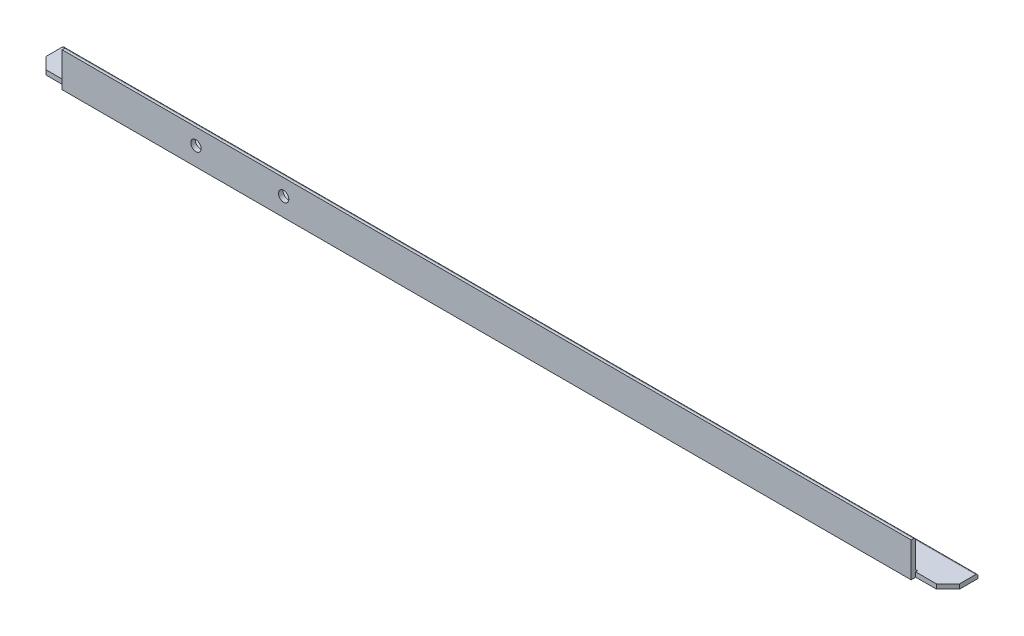
SolidWorks part; units mm, degrees
material "1060 Сплав"
ref_plane "Front" through (0, 0, 0) normal (0, 0, 1) x (1, 0, 0)
ref_plane "Top" through (0, 0, 0) normal (0, 1, 0) x (1, 0, 0)
ref_plane "Right" through (0, 0, 0) normal (1, 0, 0) x (0, 0, -1)
sketch "Эскиз1" plane through (0, 0, 0) normal (1, 0, 0) x (0, 0, -1)
  line L0 (0, 0) -> (0, 15)
  line L1 (0, 0) -> (15, 0)
  line L2 (0, 15) -> (1, 15)
  line L3 (2, 14) -> (2, 3)
  line L4 (3, 2) -> (14, 2)
  line L5 (15, 1) -> (15, 0)
  arc A0 (14, 2) -> (15, 1) centre (14, 1) cw
  arc A1 (1, 15) -> (2, 14) centre (1, 14) cw
  arc A2 (2, 3) -> (3, 2) centre (3, 3) ccw
  point P9 (15, 2)
  point P12 (2, 15)
  dimension "D5" = 1
  dimension "D1" = 15
  dimension "D2" = 15
  dimension "D3" = 2
  dimension "D4" = 2
extrude "Бобышка-Вытянуть1" add sketch "Эскиз1" along normal blind 396
sketch "Эскиз4" plane through (0, 0, 0) normal (0, -1, 0) x (1, 0, 0)
  line L0 (396, -15) -> (0, -15) construction
  line L1 (0, 0) -> (0, -15) construction
  line L2 (396, 0) -> (396, -15) construction
  circle A0 centre (371, -8) radius 2.25
  circle A1 centre (198, -8) radius 2.25
  circle A2 centre (25, -8) radius 2.25
  dimension "D1" = 4.5
  dimension "D2" = 7
  dimension "D3" = 25
  dimension "D4" = 4.5
  dimension "D5" = 25
  dimension "D6" = 7
  dimension "D7" = 173
  dimension "D8" = 4.5
extrude "Вырез-Вытянуть3" cut sketch "Эскиз4" against normal blind 2
chamfer "Фаска1" distance 2.05 angle 45 3 edges at (25, 0, -10.25) (371, 0, -10.25) (198, 0, -10.25)
sketch "Эскиз5" [suppressed] plane through (0, 2, 0) normal (0, 1, 0) x (1, 0, 0)
  line L0 (432, 14) -> (432, 3) construction
  line L1 (432, 15) -> (0, 15) construction
  line L2 (0, 14) -> (0, 3) construction
  circle A0 centre (392, 8) radius 2.3
  circle A1 centre (40, 8) radius 2.3
  dimension "D1" = 4.6
  dimension "D2" = 40
  dimension "D3" = 7
  dimension "D4" = 4.6
  dimension "D5" = 7
  dimension "D6" = 40
extrude "Вырез-Вытянуть4" [suppressed] cut sketch "Эскиз5" against normal through all
chamfer "Фаска3" [suppressed] distance 2.05 angle 45
sketch "Эскиз6" plane through (396, 0, 0) normal (1, 0, 0) x (0, 0, -1)
  line L0 (0, 0) -> (15, 0) construction
  line L1 (0, 15) -> (2, 15)
  line L2 (0, 15) -> (0, 0)
  line L3 (0, 0) -> (2, 0)
  line L4 (2, 0) -> (2, 2)
  line L5 (2, 2) -> (3, 2)
  line L6 (3, 2) -> (3, 15)
  line L7 (3, 15) -> (2, 15)
extrude "Вырез-Вытянуть5" cut sketch "Эскиз6" against normal blind 14
sketch "Эскиз7" plane through (0, 0, 0) normal (-1, 0, 0) x (0, 0, 1)
  line L0 (0, 0) -> (-15, 0) construction
  line L1 (0, 15) -> (-2, 15)
  line L2 (0, 15) -> (0, 0)
  line L3 (0, 0) -> (-2, 0)
  line L4 (-3, 2) -> (-2, 2)
  line L5 (-2, 2) -> (-2, 0)
  line L6 (-3, 2) -> (-3, 15)
  line L7 (-3, 15) -> (-2, 15)
extrude "Вырез-Вытянуть6" cut sketch "Эскиз7" against normal blind 14
sketch "Эскиз9" plane through (0, 2, 0) normal (0, 1, 0) x (1, 0, 0)
  line L0 (0, 2) -> (0, 7)
  line L1 (0, 14) -> (0, 2) construction
  line L2 (0, 7) -> (5, 2)
  line L3 (14, 2) -> (0, 2) construction
  line L4 (5, 2) -> (0, 2)
  line L5 (396, 2) -> (396, 7)
  line L6 (396, 14) -> (396, 2) construction
  line L7 (396, 7) -> (391, 2)
  line L8 (382, 2) -> (396, 2) construction
  line L9 (391, 2) -> (396, 2)
  dimension "D1" = 5
  dimension "D2" = 5
  dimension "D3" = 5
  dimension "D4" = 5
extrude "Вырез-Вытянуть7" cut sketch "Эскиз9" against normal through all
sketch "Эскиз10" plane through (0, 0, -2) normal (0, 0, -1) x (-1, 0, 0)
  line L0 (-382, 15) -> (-14, 15) construction
  line L1 (-14, 3) -> (-14, 14) construction
  circle A0 centre (-72, 8) radius 2.25
  circle A1 centre (-110, 8) radius 2.25
  dimension "D1" = 4.5
  dimension "D2" = 7
  dimension "D3" = 58
  dimension "D4" = 38
  dimension "D5" = 4.5
  dimension "D6" = 7
extrude "Вырез-Вытянуть8" cut sketch "Эскиз10" against normal through all
sketch "Эскиз11" [suppressed] plane through (0, 0, -2) normal (0, 0, -1) x (-1, 0, 0)
  line L0 (-382, 15) -> (-14, 15) construction
  line L1 (-382, 3) -> (-382, 14) construction
  circle A0 centre (-324, 8) radius 2.25
  circle A1 centre (-286, 8) radius 2.25
  dimension "D1" = 38
  dimension "D2" = 4.5
  dimension "D3" = 4.5
  dimension "D4" = 7
  dimension "D5" = 7
  dimension "D6" = 58
extrude "Вырез-Вытянуть9" [suppressed] cut sketch "Эскиз11" against normal through all
